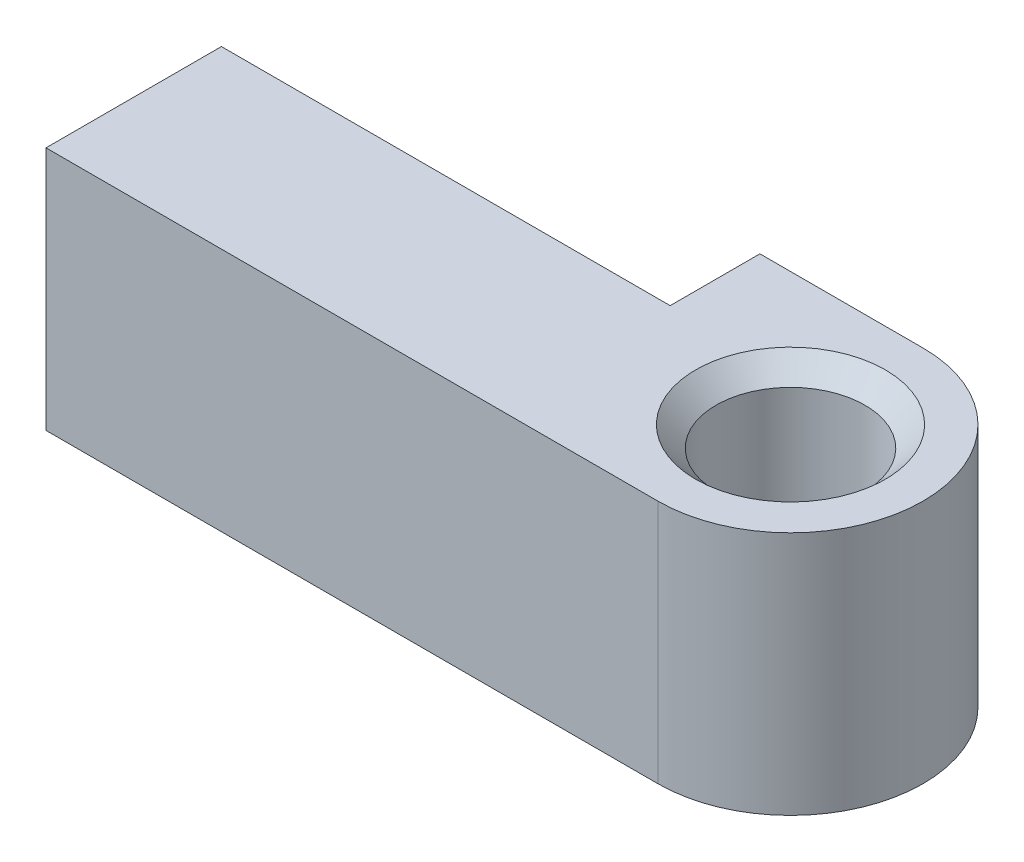
SolidWorks part; units mm, degrees
ref_plane "Front Plane" through (0, 0, 0) normal (0, 0, 1) x (1, 0, 0)
ref_plane "Top Plane" through (0, 0, 0) normal (0, 1, 0) x (1, 0, 0)
ref_plane "Right Plane" through (0, 0, 0) normal (1, 0, 0) x (0, 0, -1)
sketch "Sketch2" plane through (0, 0, 0) normal (0, 1, 0) x (1, 0, 0)
  line L1 (11, 2.2) -> (15, 2.2)
  line L2 (0, 0) -> (0, -4.3)
  line L3 (0, -4.3) -> (15, -4.3)
  line L7 (0, 0) -> (11, 0)
  line L8 (11, 2.2) -> (11, 0)
  arc A0 (15, -4.3) -> (15, 2.2) centre (15, -1.05) ccw
  circle A1 centre (15, -1.05) radius 1.825
  point P9 (0, 0)
  dimension "D5" = 3.65
  dimension "D1" = 6.5
  dimension "D2" = 15
  dimension "D3" = 11
  dimension "D4" = 2.2
extrude "Boss-Extrude1" add sketch "Sketch2" along normal blind 6
chamfer "Chamfer1" distance 0.5 angle 45 1 edges at (15, 6, 2.875)
